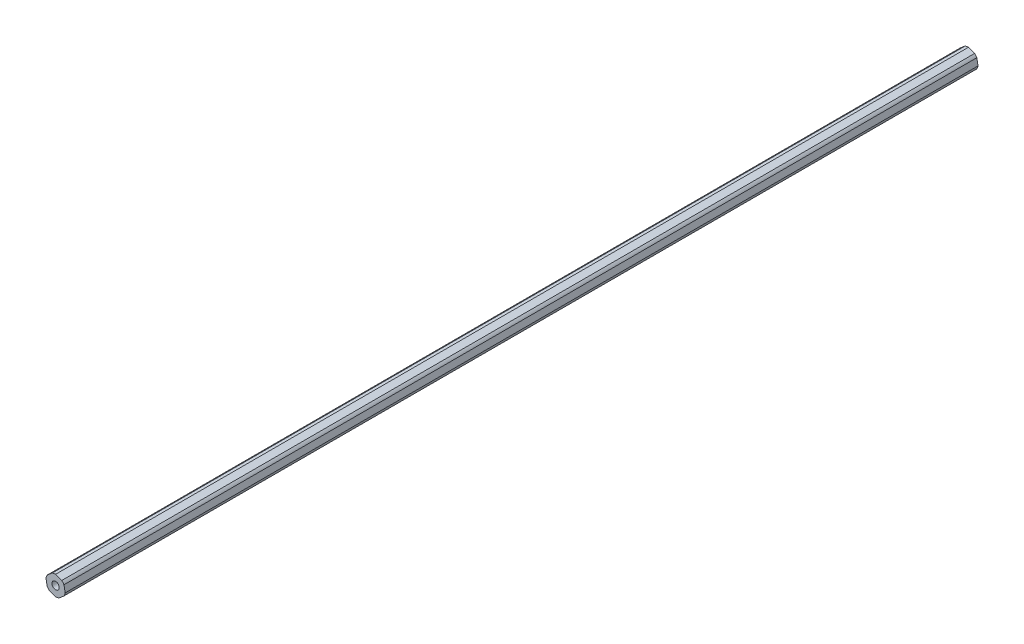
SolidWorks part; units mm, degrees
material "7075-T6 (SN)"
ref_plane "Front Plane" through (0, 0, 0) normal (0, 0, 1) x (1, 0, 0)
ref_plane "Top Plane" through (0, 0, 0) normal (0, 1, 0) x (1, 0, 0)
ref_plane "Right Plane" through (0, 0, 0) normal (1, 0, 0) x (0, 0, -1)
sketch "Sketch1" plane through (0, 0, 0) normal (0, 0, 1) x (1, 0, 0)
  line L1 (-6.6545, 1.1312) -> (-5.8457, -3.375)
  line L2 (-4.3069, -5.1974) -> (0, -6.75)
  line L3 (2.3476, -6.3286) -> (5.8457, -3.375)
  line L4 (6.6545, -1.1312) -> (5.8457, 3.375)
  line L5 (4.3069, 5.1974) -> (0, 6.75)
  line L6 (-2.3476, 6.3286) -> (-5.8457, 3.375)
  circle A0 centre (0, 0) radius 6.35 construction
  arc A1 (-5.8457, 3.375) -> (-6.6545, 1.1312) centre (0, 0) ccw
  arc A2 (-5.8457, -3.375) -> (-4.3069, -5.1974) centre (0, 0) ccw
  arc A3 (0, -6.75) -> (2.3476, -6.3286) centre (0, 0) ccw
  arc A4 (5.8457, -3.375) -> (6.6545, -1.1312) centre (0, 0) ccw
  arc A5 (5.8457, 3.375) -> (4.3069, 5.1974) centre (0, 0) ccw
  arc A6 (0, 6.75) -> (-2.3476, 6.3286) centre (0, 0) ccw
  dimension "D1" = 12.7
  dimension "D2" = 13.5
extrude "Boss-Extrude1" add sketch "Sketch1" along normal blind 635
sketch "Sketch2" plane through (0, 0, 635) normal (0, 0, 1) x (1, 0, 0)
  circle A0 centre (0, 0) radius 2.0193
  dimension "D1" = 4.0386
extrude "Cut-Extrude1" cut sketch "Sketch2" against normal through all
hole_wizard "1/4-20 Tapped Hole1" positions "Sketch5" profile "Sketch6" tap size "1/4-20" standard "ANSI Inch"
sketch "Sketch5" plane through (0, 0, 635) normal (0, 0, 1) x (1, 0, 0)
  point P0 (0, 0)
sketch "Sketch6" plane through (0, 0, 635) normal (1, 0, 0) x (0, -1, 0)
  line L0 (0, 0) -> (0, 20.5838)
  line L1 (0, 20.5838) -> (2.5527, 19.05)
  line L2 (2.5527, 19.05) -> (2.5527, 0)
  line L5 (2.5527, 0) -> (0, 0)
  line L10 (0, 20.5838) -> (-2.5527, 19.05) construction
  line L11 (0, -6.35) -> (0, 107.95) construction
  dimension "Tap Drill Dia." = 5.1054
  dimension "Tap Drill Depth" = 19.05
  dimension "Drill Angle" = 118
cosmetic thread "Hole Thread1" parameters "D1"=12.7, "D2"=6.35
hole_wizard "1/4-20 Tapped Hole2" positions "Sketch7" profile "Sketch8" tap size "1/4-20" standard "ANSI Inch"
sketch "Sketch7" plane through (0, 0, 0) normal (0, 0, -1) x (-1, 0, 0)
  point P0 (0, 0)
sketch "Sketch8" plane through (0, 0, 0) normal (1, 0, 0) x (0, 1, 0)
  line L0 (0, 0) -> (0, 20.5838)
  line L1 (0, 20.5838) -> (2.5527, 19.05)
  line L2 (2.5527, 19.05) -> (2.5527, 0)
  line L5 (2.5527, 0) -> (0, 0)
  line L10 (0, 20.5838) -> (-2.5527, 19.05) construction
  line L11 (0, -6.35) -> (0, 107.95) construction
  dimension "Tap Drill Dia." = 5.1054
  dimension "Tap Drill Depth" = 19.05
  dimension "Drill Angle" = 118
cosmetic thread "Hole Thread2" parameters "D1"=12.7, "D2"=6.35
